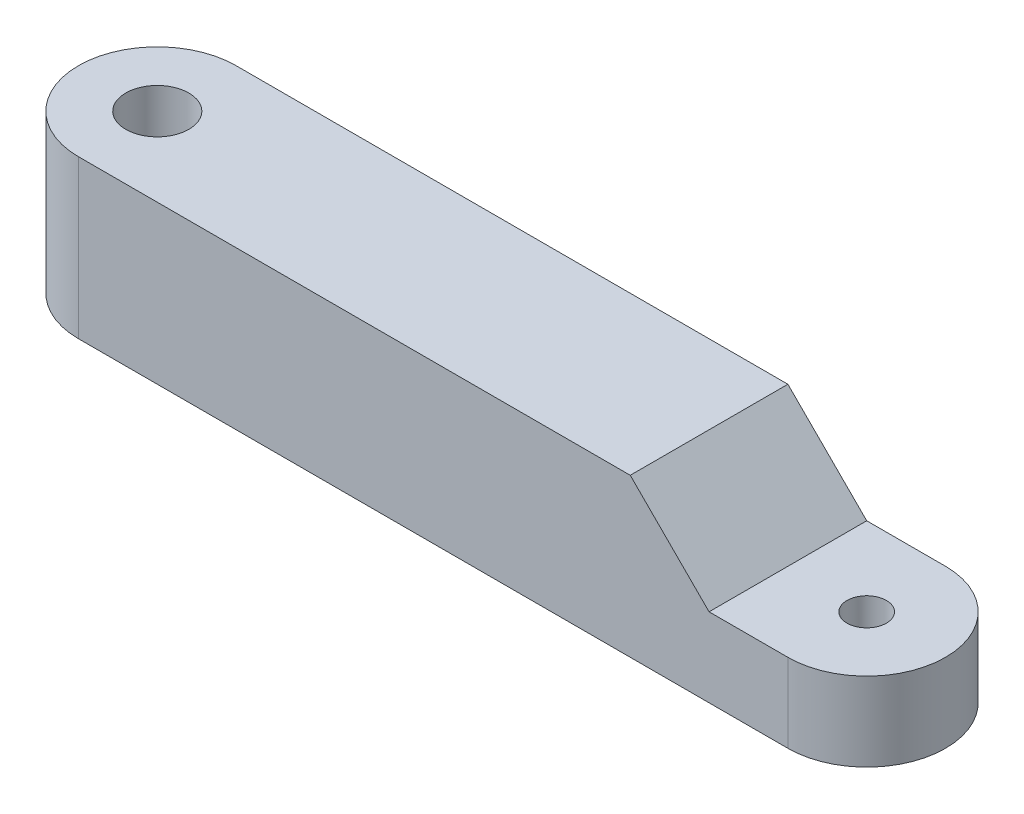
SolidWorks part; units mm, degrees
ref_plane "Plan de face" through (0, 0, 0) normal (0, 0, 1) x (1, 0, 0)
ref_plane "Plan de dessus" through (0, 0, 0) normal (0, 1, 0) x (1, 0, 0)
ref_plane "Plan de droite" through (0, 0, 0) normal (1, 0, 0) x (0, 0, -1)
sketch "Esquisse1" plane through (0, 0, 0) normal (0, 1, 0) x (1, 0, 0)
  line L1 (0, 5) -> (45, 5)
  line L3 (0, -5) -> (45, -5)
  circle A0 centre (0, 0) radius 2
  arc A1 (45, 5) -> (45, -5) centre (45, 0) cw
  arc A2 (0, 5) -> (0, -5) centre (0, 0) ccw
  dimension "D3" = 4
  dimension "D1" = 10
  dimension "D2" = 45
extrude "Boss.-Extru.1" add sketch "Esquisse1" along normal mid plane 10
hole_wizard "Trou taraudé M3x0.51" positions "Esquisse3" profile "Esquisse2" tap size "M3x0.5" standard "Ansi Metric" end condition through all
sketch "Esquisse3" plane through (0, 5, 0) normal (0, 1, 0) x (1, 0, 0)
  arc A0 (45, -5) -> (45, 5) centre (45, 0) ccw construction
  point P0 (45, 0)
sketch "Esquisse2" plane through (45, 5, 0) normal (1, 0, 0) x (0, 0, 1)
  line L0 (0, 0) -> (0, 10)
  line L1 (0, 10) -> (1.25, 10)
  line L2 (1.25, 10) -> (1.25, 0.275)
  line L3 (1.25, 0.275) -> (1.525, 0)
  line L5 (1.525, 0) -> (0, 0)
  line L6 (-1.25, 0.275) -> (-1.525, 0) construction
  line L11 (0, -6.35) -> (0, 107.95) construction
  dimension "Diamètre du trou pour taraudage jusqu'au prochain" = 2.5
  dimension "Profondeur du trou pour taraudage jusqu'au prochain" = 10
  dimension "Diamètre du fraisage entrant" = 3.05
  dimension "Angle du fraisage entrant" = 90
cosmetic thread "Filetage de perçage1" parameters "D2"=3
sketch "Esquisse4" plane through (0, 0, 0) normal (0, 0, 1) x (1, 0, 0)
  line L0 (0, 5) -> (45, 5) construction
  line L1 (35, 5) -> (50, 5)
  line L2 (35, 5) -> (40, 0)
  line L3 (40, 0) -> (50, 0)
  line L4 (50, 5) -> (50, 0)
  line L5 (50, -5) -> (50, 5) construction
  line L6 (0, -5) -> (45, -5) construction
  dimension "D1" = 15
  dimension "D2" = 5
  dimension "D3" = 45
extrude "Enlèv. mat.-Extru.1" cut sketch "Esquisse4" against normal through all and the other way through all
